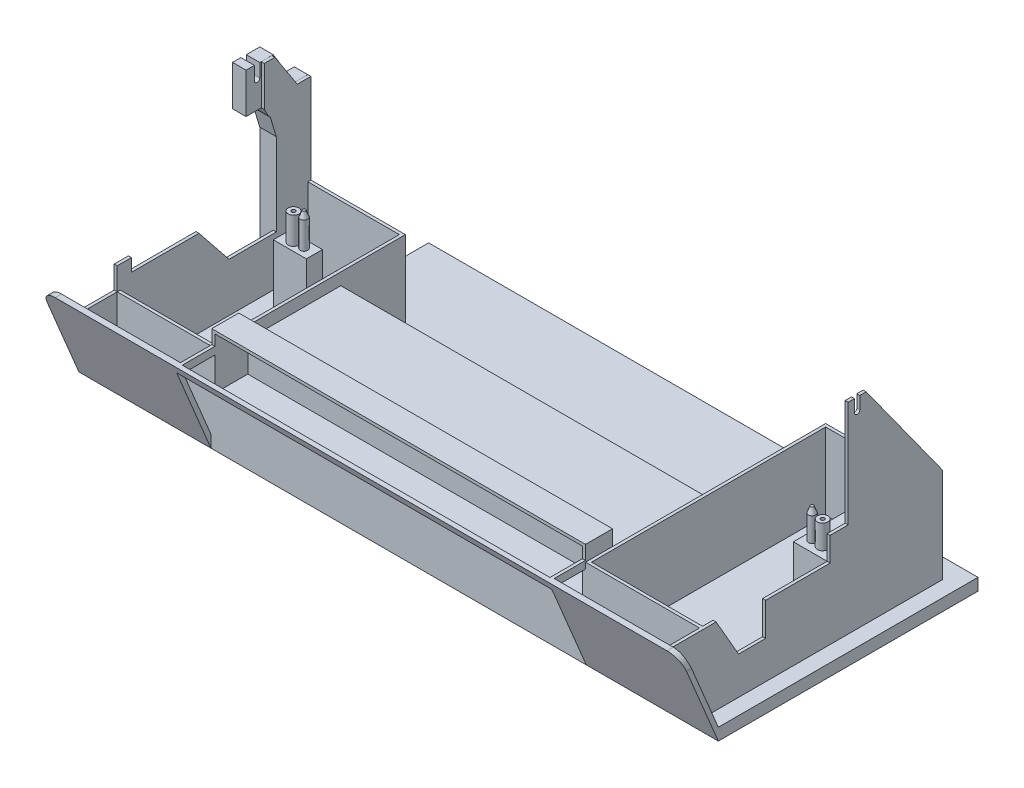
SolidWorks part; units mm, degrees
ref_plane "Alzado" through (0, 0, 0) normal (0, 0, 1) x (1, 0, 0)
ref_plane "Planta" through (0, 0, 0) normal (0, 1, 0) x (1, 0, 0)
ref_plane "Vista lateral" through (0, 0, 0) normal (1, 0, 0) x (0, 0, -1)
sketch "Croquis1" plane through (0, 0, 0) normal (0, 1, 0) x (1, 0, 0)
  line L1 (213, -91.5) -> (-213, -91.5)
  line L2 (213, -91.5) -> (213, 91.5)
  line L3 (213, 91.5) -> (-213, 91.5)
  line L4 (-213, -91.5) -> (-213, 91.5)
  line L5 (213, -91.5) -> (-213, 91.5) construction
  line L6 (213, 91.5) -> (-213, -91.5) construction
  line L7 (213, 91.5) -> (163, 91.5)
  line L8 (213, 91.5) -> (213, 81.5)
  line L9 (213, 81.5) -> (163, 81.5)
  line L10 (163, 91.5) -> (163, 81.5)
  line L11 (-213, 91.5) -> (-163, 91.5)
  line L12 (-213, 91.5) -> (-213, 46.5)
  line L13 (-213, 46.5) -> (-163, 46.5)
  line L14 (-163, 91.5) -> (-163, 46.5)
  point P0 (0, 0)
  dimension "D1" = 183
  dimension "D2" = 426
  dimension "D3" = 10
  dimension "D4" = 50
  dimension "D5" = 45
  dimension "D6" = 50
extrude "Saliente-Extruir3" add sketch "Croquis1" along normal blind 8 contours L3 L14 L13 L4 L1 L2 L9 L10 region at (4.3745, 0, 2.6393)
sketch "Croquis4" plane through (0, 0, 0) normal (0, -1, 0) x (1, 0, 0)
  line L1 (-213, 91.5) -> (212.5, 91.5)
  line L2 (-213, 91.5) -> (-213, 117.5)
  line L3 (-213, 117.5) -> (212.5, 117.5)
  line L4 (212.5, 91.5) -> (212.5, 117.5)
  dimension "D1" = 26
extrude "Saliente-Extruir5" add sketch "Croquis4" against normal blind 70 separate body
sketch "Croquis5" plane through (-213, 0, 0) normal (-1, 0, 0) x (0, 0, 1)
  line L0 (91.5, 8) -> (91.5, 5.5)
  line L2 (91.5, 8) -> (98.5, 8)
  line L3 (91.5, 70) -> (91.5, 0) construction
  line L4 (91.5, 5.5) -> (99.5, 5.5)
  line L10 (117.5, 0) -> (91.5, 0) construction
  line L11 (91.5, 70) -> (117.5, 70)
  line L12 (91.5, 70) -> (91.5, 0)
  line L13 (91.5, 0) -> (117.5, 0)
  line L14 (117.5, 70) -> (117.5, 0)
  line L15 (117.5, 70) -> (115, 70)
  line L16 (115, 70) -> (98.5, 8)
  line L17 (99.5, 5.5) -> (117.5, 70)
  line M12 (91.5, 0) -> (117.5, 0)
  line M13 (117.5, 0) -> (117.5, 70)
  line M15 (91.5, 70) -> (91.5, 0)
  dimension "D1" = 2.5
  dimension "D2" = 8
  dimension "D3" = 2.5
extrude "Cortar-Extruir5" cut sketch "Croquis5" against normal through all contours L16 L11 L2 M15 | L17 L4 M15 M12 M13 region at (-213, 44.5902, 99.8689) region at (-213, 22.207, 110.1164)
fillet "Redondeo2" radius 1 3 edges at (-0.25, 70, 115) (-0.25, 70, 117.5) (-0.25, 5.5, 99.5)
sketch "Croquis7" plane through (0, 0, 91.5) normal (0, 0, 1) x (1, 0, 0)
  line L1 (213, 0) -> (-213, 0) construction
  line L3 (-122.5, 0) -> (122.5, 0)
  line L4 (-122.5, 0) -> (-122.5, 65)
  line L5 (-122.5, 65) -> (122.5, 65)
  line L6 (122.5, 0) -> (122.5, 65)
  dimension "D2" = 65
  dimension "D3" = 245
extrude "Cortar-Extruir6" cut sketch "Croquis7" along normal blind 25
sketch "Croquis8" plane through (0, 8, 0) normal (0, 1, 0) x (1, 0, 0)
  line L1 (-122.5, -91.5) -> (122.5, -91.5)
  line L2 (-122.5, -91.5) -> (-122.5, -69.5)
  line L3 (-122.5, -69.5) -> (122.5, -69.5)
  line L4 (122.5, -91.5) -> (122.5, -69.5)
  dimension "D1" = 22
extrude "Saliente-Extruir6" add sketch "Croquis8" along normal blind 25
sketch "Croquis9" plane through (-122.5, 0, 0) normal (-1, 0, 0) x (0, 0, 1)
  line L2 (114.8023, 69.2572) -> (98.5, 8)
  line L4 (98.5, 8) -> (73.5, 8)
  line L5 (98.5, 8) -> (-46.5, 8) construction
  line L6 (73.5, 8) -> (73.5, 69.2572)
  line L7 (73.5, 69.2572) -> (114.8023, 69.2572)
  dimension "D1" = 25
extrude "Saliente-Extruir7" add sketch "Croquis9" along normal blind 2
sketch "Croquis10" plane through (122.5, 0, 0) normal (1, 0, 0) x (0, 0, -1)
  line L5 (-91.5, 8) -> (-69.5, 8) construction
  line L6 (-73.5, 8) -> (-73.5, 69.2572)
  line L8 (-73.5, 69.2572) -> (-114.8023, 69.2572)
  line L9 (-114.8023, 69.2572) -> (-98.5, 8)
  line L10 (-98.5, 8) -> (-73.5, 8)
extrude "Saliente-Extruir8" add sketch "Croquis10" along normal blind 2
sketch "Croquis13" plane through (-122.5, 0, 0) normal (1, 0, 0) x (0, 0, -1)
  line L2 (-114.8023, 69.2572) -> (-114.8023, 67.2572)
  line L5 (-114.8023, 69.2572) -> (-73.5, 69.2572)
  line L6 (-73.5, 69.2572) -> (-73.5, 67.2572)
  line L7 (-73.5, 69.2572) -> (-73.5, 33) construction
  line L8 (-114.8023, 67.2572) -> (-73.5, 67.2572)
  dimension "D1" = 2
extrude "Saliente-Extruir13" add sketch "Croquis13" along normal up to surface (245 mm away) up to face at (122.5, 39.0648, 97.016)
sketch "Croquis15" plane through (0, 8, 0) normal (0, 1, 0) x (1, 0, 0)
  line L1 (213, -91.5) -> (213, 81.5) construction
  line L2 (213, -73.5) -> (213, -71.5)
  line L15 (124.5, -91.5) -> (202.5, -91.5)
  line L21 (124.5, -98.5) -> (124.5, -91.5)
  line L22 (124.5, -98.5) -> (124.5, -73.5) construction
  line L26 (202.5, -91.5) -> (202.5, 68.5)
  line L28 (126.5, -89.5) -> (200.5, -89.5)
  line L30 (202.5, 68.5) -> (124.5, 68.5)
  line L31 (124.5, -91.5) -> (124.5, 68.5)
  line L32 (124.5, 68.5) -> (124.5, 66.5) construction
  line L33 (124.5, 66.5) -> (126.5, 66.5) construction
  line L34 (126.5, 66.5) -> (126.5, -89.5)
  line L35 (126.5, 66.5) -> (200.5, 66.5)
  line L36 (200.5, 66.5) -> (200.5, -89.5)
  dimension "D2" = 160
  dimension "D1" = 7
  dimension "D3" = 2
  dimension "D4" = 2
extrude "Saliente-Extruir15" add sketch "Croquis15" along normal blind 51 contours L15 L26 L30 L31 | L28 L36 L35 L34
sketch "Croquis16" plane through (0, 8, 0) normal (0, 1, 0) x (1, 0, 0)
  line L1 (-122.5, -69.5) -> (122.5, -69.5)
  line L2 (-122.5, -69.5) -> (-122.5, -5.5)
  line L3 (-122.5, -5.5) -> (122.5, -5.5)
  line L4 (122.5, -69.5) -> (122.5, -5.5)
  dimension "D1" = 64
extrude "Saliente-Extruir16" add sketch "Croquis16" along normal blind 43
sketch "Croquis17" plane through (0, 8, 0) normal (0, 1, 0) x (1, 0, 0)
  line L1 (122.5, -5.5) -> (124.5, -5.5)
  line L2 (122.5, -5.5) -> (122.5, -73.5)
  line L3 (122.5, -73.5) -> (124.5, -73.5)
  line L4 (124.5, -5.5) -> (124.5, -73.5)
  line L6 (124.5, -73.5) -> (124.5, 68.5) construction
  line L7 (124.5, -73.5) -> (122.5, -73.5) construction
  dimension "D1" = 68
extrude "Saliente-Extruir18" add sketch "Croquis17" along normal up to surface (43 mm away) up to face at (0, 51, 37.5)
sketch "Croquis18" plane through (202.5, 0, 0) normal (1, 0, 0) x (0, 0, -1)
  line L0 (-91.5, 8) -> (-98.5, 8)
  line L1 (-98.5, 8) -> (-112.0726, 59)
  line L2 (-114.8023, 69.2572) -> (-98.5, 8) construction
  line L3 (-112.0726, 59) -> (-91.5, 59)
  line L4 (-91.5, 59) -> (-91.5, 8)
extrude "Saliente-Extruir21" add sketch "Croquis18" against normal blind 2
sketch "Croquis20" plane through (0, 59, 0) normal (0, 1, 0) x (1, 0, 0)
  line L1 (200.5, -91.5) -> (202.5, -91.5)
  line L2 (200.5, -91.5) -> (200.5, 68.5)
  line L3 (200.5, 68.5) -> (202.5, 68.5)
  line L4 (202.5, -91.5) -> (202.5, 68.5)
extrude "Saliente-Extruir22" add sketch "Croquis20" along normal blind 100
sketch "Croquis21" plane through (202.5, 0, 0) normal (1, 0, 0) x (0, 0, -1)
  line L0 (-91.5, 59) -> (-82.5, 59)
  line L3 (-67.5, 33) -> (-82.5, 59)
  line L4 (-67.5, 33) -> (-49.5, 33)
  line L5 (-49.5, 33) -> (-49.5, 55)
  line L6 (-49.5, 55) -> (-6.5, 55)
  line L7 (-6.5, 55) -> (-6.5, 71)
  line L8 (-6.5, 71) -> (5.5, 71)
  line L9 (5.5, 71) -> (5.5, 141.8)
  line L11 (17.5, 141.8) -> (68.5, 71)
  line L12 (68.5, 159) -> (68.5, 8) construction
  line L13 (-91.5, 59) -> (-91.5, 159)
  line L14 (-91.5, 159) -> (68.5, 159)
  line L15 (68.5, 159) -> (68.5, 71)
  line L16 (5.5, 141.8) -> (9.7, 141.8)
  line L17 (9.7, 141.8) -> (9.7, 133.6)
  line L18 (17.5, 141.8) -> (13.3, 141.8)
  line L19 (13.3, 141.8) -> (13.3, 133.6)
  line L20 (-82.5, 59) -> (-82.5, 33) construction
  line L21 (-82.5, 33) -> (-67.5, 33) construction
  arc A0 (9.7, 133.6) -> (13.3, 133.6) centre (11.5, 133.6) ccw
  dimension "D12" = 6
  dimension "D1" = 9
  dimension "D2" = 18
  dimension "D3" = 22
  dimension "D4" = 43
  dimension "D5" = 16
  dimension "D6" = 12
  dimension "D7" = 70.8
  dimension "D8" = 12
  dimension "D9" = 4.2
  dimension "D10" = 8.2
  dimension "D11" = 4.2
  dimension "D13" = 26
extrude "Cortar-Extruir7" cut sketch "Croquis21" against normal blind 2
sketch "Croquis22" plane through (0, 8, 0) normal (0, 1, 0) x (1, 0, 0)
  line L1 (-124.5, -73.5) -> (-122.5, -73.5)
  line L2 (-124.5, -73.5) -> (-124.5, -5.5)
  line L3 (-124.5, -5.5) -> (-122.5, -5.5)
  line L4 (-122.5, -73.5) -> (-122.5, -5.5)
extrude "Saliente-Extruir23" add sketch "Croquis22" along normal up to surface (43 mm away) up to face at (41.5, 51, 49.5)
sketch "Croquis23" plane through (0, 8, 0) normal (0, 1, 0) x (1, 0, 0)
  line L0 (-124.5, -91.5) -> (-124.5, -89.5) construction
  line L1 (-124.5, -98.5) -> (-124.5, -91.5) construction
  line L2 (-124.5, -5.5) -> (-124.5, -98.5) construction
  line L3 (-124.5, -89.5) -> (-126.5, -89.5) construction
  line L4 (-124.5, -91.5) -> (-189.5, -91.5)
  line L5 (-124.5, -91.5) -> (-124.5, 37.5)
  line L6 (-124.5, 37.5) -> (-189.5, 37.5)
  line L7 (-189.5, -91.5) -> (-189.5, 37.5)
  line L9 (-126.5, -89.5) -> (-187.5, -89.5)
  line L10 (-126.5, -89.5) -> (-126.5, 35.5)
  line L11 (-126.5, 35.5) -> (-187.5, 35.5)
  line L12 (-187.5, -89.5) -> (-187.5, 35.5)
  dimension "D1" = 7
  dimension "D2" = 129
  dimension "D3" = 65
  dimension "D4" = 2
  dimension "D5" = 2
  dimension "D6" = 125
  dimension "D7" = 61
extrude "Saliente-Extruir24" add sketch "Croquis23" along normal up to surface (51 mm away) up to face at (171.8846, 59, 42.665)
sketch "Croquis26" plane through (-189.5, 0, 0) normal (-1, 0, 0) x (0, 0, 1)
  line L0 (91.5, 8) -> (98.5, 8)
  line L5 (91.5, 59) -> (91.5, 8)
  line L6 (91.5, 59) -> (112.0726, 59)
  line L7 (114.8023, 69.2572) -> (98.5, 8) construction
  line L8 (112.0726, 59) -> (98.5, 8)
extrude "Saliente-Extruir26" add sketch "Croquis26" against normal blind 2
sketch "Croquis27" plane through (0, 51, 0) normal (0, 1, 0) x (1, 0, 0)
  line L7 (-189.5, 37.5) -> (-187.5, 37.5)
  line L8 (-189.5, 37.5) -> (-189.5, -91.5)
  line L9 (-189.5, -91.5) -> (-187.5, -91.5)
  line L10 (-187.5, 37.5) -> (-187.5, -91.5)
extrude "Saliente-Extruir27" add sketch "Croquis27" along normal blind 150
sketch "Croquis28" plane through (-189.5, 0, 0) normal (-1, 0, 0) x (0, 0, 1)
  line L0 (91.5, 59) -> (91.5, 74)
  line L1 (91.5, 201) -> (91.5, 59) construction
  line L2 (91.5, 74) -> (82, 74)
  line L3 (82, 74) -> (82, 65.5)
  line L4 (82, 65.5) -> (37, 65.5)
  line L7 (17, 40.5) -> (37, 65.5)
  line L8 (-37.5, 40.5) -> (-14.5, 40.5) construction
  line L9 (-37.5, 201) -> (-37.5, 8) construction
  line L10 (17, 40.5) -> (-14.5, 40.5)
  line L11 (-14.5, 40.5) -> (-14.5, 95.5)
  line L13 (-37.5, 118.7922) -> (-37.5, 201)
  line L17 (-28.5, 118.7922) -> (-13.5, 141.7922)
  line L18 (-28.5, 118.7922) -> (-37.5, 118.7922)
  line L19 (-14.5, 95.5) -> (-10.5263, 108.6789)
  line L22 (-37.5, 201) -> (91.5, 201)
  line L23 (91.5, 201) -> (91.5, 74)
  line L29 (-37.5, 118.7922) -> (-37.5, 201)
  line L30 (91.5, 201) -> (91.5, 74)
  line L31 (-13.5, 141.7922) -> (-13.5, 118.7922) construction
  line L32 (-10.5263, 108.6789) -> (-8.9353, 110.5946)
  line L33 (-13.5, 141.7922) -> (-6.5, 141.7922)
  line L34 (-13.5, 118.7922) -> (-28.5, 118.7922) construction
  line L35 (-6.5, 141.7922) -> (-6.5, 115.1522)
  line L36 (-6.5, 115.1522) -> (-8.9353, 110.5946)
  line L37 (-37.5, 118.7922) -> (-37.5, 8)
  line L38 (-37.5, 8) -> (-37.5, 118.7922)
  line M3 (91.5, 59) -> (91.5, 201)
  line M4 (91.5, 201) -> (-37.5, 201)
  line M5 (-37.5, 201) -> (-37.5, 8)
  dimension "D5" = 23
  dimension "D1" = 15
  dimension "D2" = 9.5
  dimension "D3" = 8.5
  dimension "D4" = 45
  dimension "D6" = 55
  dimension "D7" = 7
extrude "Cortar-Extruir9" cut sketch "Croquis28" against normal blind 2 contours L19 L11 L10 L7 L4 L3 L2 L18 L17 M3 M4 M5 region at (-189.5, 131.8802, 30.3674)
sketch "Croquis29" plane through (-189.5, 0, 0) normal (-1, 0, 0) x (0, 0, 1)
  line L1 (-37.5, 8) -> (-14.5, 8)
  line L2 (-37.5, 8) -> (-37.5, 118.8)
  line L11 (-14.5, 95.5) -> (-14.5, 8)
  line L33 (-14.5, 95.5) -> (-10.5263, 108.6789)
  line L41 (-10.5263, 108.6789) -> (-8.9353, 110.5946)
  line L42 (-8.9353, 110.5946) -> (-6.5, 115.1522)
  line L43 (-6.5, 115.1522) -> (3.6557, 115.1522)
  line L45 (-37.5, 118.8) -> (-28.5, 118.8)
  line L48 (-5.5, 71) -> (-5.5, 141.8) construction
  line L51 (-1.9, 132.9522) -> (-1.9, 141.9522)
  line L52 (-1.9, 141.9522) -> (3.6557, 141.9522)
  line L53 (3.6557, 141.9522) -> (3.6557, 115.1522)
  line L54 (-5.5, 132.9522) -> (-5.5, 141.8)
  line L55 (-5.5, 141.8) -> (-14.5, 141.8)
  line L56 (-14.5, 141.8) -> (-28.5, 118.8)
  arc A2 (-5.5, 132.9522) -> (-1.9, 132.9522) centre (-3.7, 132.9522) ccw
  dimension "D5" = 26.8
  dimension "D1" = 110.8
  dimension "D2" = 23
  dimension "D3" = 9
  dimension "D4" = 3.6
extrude "Saliente-Extruir28" add sketch "Croquis29" along normal blind 9
sketch "Croquis33" plane through (0, 8, 0) normal (0, 1, 0) x (1, 0, 0)
  line L0 (-124.5, 37.5) -> (-124.5, 1.87) construction
  line L1 (-124.5, -5.5) -> (-124.5, 37.5) construction
  line L2 (-124.5, 1.87) -> (-149.5, 1.87) construction
  line L3 (-149.5, -3.48) -> (-149.5, 7.22)
  line L4 (-149.5, 7.22) -> (-171.5, 7.22)
  line L5 (-171.5, 7.22) -> (-171.5, -3.48)
  line L6 (-171.5, -3.48) -> (-149.5, -3.48)
  point P9 (-149.5, 1.87)
  dimension "D1" = 35.63
  dimension "D2" = 25
  dimension "D3" = 5.35
  dimension "D4" = 22
extrude "Saliente-Extruir29" add sketch "Croquis33" along normal blind 45
sketch "Croquis34" plane through (0, 53, 0) normal (0, 1, 0) x (1, 0, 0)
  line L0 (-159.9, 3) -> (-158.9, 3)
  line L1 (-171.5, -3.48) -> (-171.5, 1.87) construction
  line L2 (-158.9, 3) -> (-156.4, 3)
  line L3 (-171.5, 7.22) -> (-171.5, -3.48) construction
  line L4 (-171.5, 1.87) -> (-163.4, 1.87) construction
  line L6 (-156.4, 1.87) -> (-163.4, 1.87) construction
  circle A3 centre (-163.4, 1.87) radius 1.25
  circle A4 centre (-163.4, 1.87) radius 3.5
  circle A5 centre (-156.4, 1.87) radius 2.5
  dimension "D3" = 7
  dimension "D1" = 2.5
  dimension "D5" = 5
  dimension "D2" = 1
  dimension "D4" = 2.5
extrude "Saliente-Extruir30" add sketch "Croquis34" along normal blind 18 contours A3 | A5 region at (-166.801, 53, -1.87)
sketch "Croquis36" plane through (200.5, 0, 0) normal (-1, 0, 0) x (0, 0, 1)
  line L7 (6.5, 55) -> (-29, 55)
  line L12 (6.5, 55) -> (6.5, 8)
  line L13 (6.5, 8) -> (-29, 8)
  line L14 (-29, 55) -> (-29, 8)
  line L15 (-66.5, 8) -> (89.5, 8) construction
  dimension "D1" = 47
  dimension "D2" = 35.5
extrude "Saliente-Extruir34" add sketch "Croquis36" along normal blind 22.5
sketch "Croquis37" plane through (0, 71, 0) normal (0, 1, 0) x (1, 0, 0)
  line L0 (202.5, 5.5) -> (202.5, 0.5) construction
  line L1 (202.5, -6.5) -> (202.5, 5.5) construction
  line L2 (202.5, 0.5) -> (194, 0.5) construction
  line L3 (194, 0.5) -> (190.5, 0.5) construction
  line L4 (187, 0.5) -> (186, 0.5)
  line L5 (186, 0.5) -> (183.5, 0.5)
  circle A0 centre (190.5, 0.5) radius 3.5
  circle A1 centre (183.5, 0.5) radius 2.5
  circle A2 centre (190.5, 0.5) radius 1.25
  dimension "D4" = 7
  dimension "D7" = 5
  dimension "D8" = 2.5
  dimension "D1" = 5
  dimension "D2" = 8.5
  dimension "D3" = 3.5
  dimension "D5" = 1
  dimension "D6" = 2.5
extrude "Saliente-Extruir35" add sketch "Croquis37" against normal up to next contours A0 A2 | A1 region at (181.0707, 71, -0.5) region at (190.5, 71, -3.901)
sketch "Croquis39" plane through (0, 71, 0) normal (0, 1, 0) x (1, 0, 0)
  circle A0 centre (-156.4, 1.87) radius 1
  dimension "D1" = 2
extrude "Saliente-Extruir37" add sketch "Croquis39" along normal blind 4
loft "Recubrir3" add section edge at (-156.4, 71, 0.63) section edge at (-156.4, 75, -0.87) connector at (-157.8182, 71, 0.1888) connector at (-156.4778, 75, -0.873)
sketch "Croquis41" plane through (0, 71, 0) normal (0, 1, 0) x (1, 0, 0)
  circle A0 centre (183.5, 0.5) radius 1
  dimension "D1" = 2
extrude "Saliente-Extruir38" add sketch "Croquis41" along normal blind 4
loft "Recubrir4" add section edge at (183.5, 75, 0.5) section edge at (183.5, 71, 2) connector at (184.219, 75, 0.195) connector at (184.2201, 71, 1.8941)
sketch "Croquis42" plane through (-213, 0, 0) normal (-1, 0, 0) x (0, 0, 1)
  line L0 (91.5, 0) -> (91.5, 60)
  line L1 (91.5, 60) -> (116.5, 60)
  line L2 (116.5, 60) -> (91.5, 0)
  line L3 (91.5, 0) -> (91.5, 8)
  line L4 (98.5, 8) -> (-46.5, 8) construction
  line L5 (91.5, 8) -> (113.1667, 60)
  line M5 (91.5, 0) -> (91.5, 5.5)
  line M6 (91.5, 5.5) -> (98.7409, 5.5)
  line M8 (99.7041, 6.2312) -> (117.1459, 68.7312)
  line M12 (114.8023, 69.2572) -> (98.5, 8)
  line M13 (98.5, 8) -> (-46.5, 8)
  dimension "D1" = 60
  dimension "D2" = 25
extrude "Saliente-Extruir39" add sketch "Croquis42" against normal through all contours L2 L1 M8 | L5 L2 L1 M12 M8 | L5 L2 M13 M12 | L2 L0 M13 M6 | L2 M6 M5 region at (-213, 3.6667, 92.2639) region at (-213, 6.8272, 92.9223) region at (-213, 26.2909, 100.6143) region at (-213, 49.0965, 110.4746) region at (-213, 55.662, 114.0956)
sketch "Croquis43" plane through (-213, 0, 0) normal (-1, 0, 0) x (0, 0, 1)
  line L0 (116.5, 60) -> (91.5, 0)
  line L1 (116.5, 60) -> (116.5, 0)
  line L2 (116.5, 0) -> (91.5, 0)
extrude "Cortar-Extruir10" cut sketch "Croquis43" against normal through all
sketch "Croquis44" plane through (-213, 0, 0) normal (-1, 0, 0) x (0, 0, 1)
  line L0 (91.5, 74) -> (91.5, 59) construction
  line L1 (116.5, 60) -> (91.5, 60)
  line L3 (116.5, 70.5118) -> (91.5, 70.5118)
  line L4 (91.5, 60) -> (91.5, 70.5118)
  line L6 (116.5, 70.5118) -> (118.3191, 70.5118)
  line L8 (116.5, 60) -> (118.3191, 60)
  line L9 (118.3191, 70.5118) -> (118.3191, 60)
extrude "Cortar-Extruir11" cut sketch "Croquis44" against normal through all
sketch "Croquis46" plane through (0, 0, 91.5) normal (0, 0, 1) x (1, 0, 0)
  line L0 (125, 0) -> (-125, 0)
  line L1 (213, 0) -> (-213, 0) construction
  line L2 (-125, 0) -> (-125, 55)
  line L3 (-125, 55) -> (125, 55)
  line L4 (125, 55) -> (125, 0)
  point P5 (0, 0)
  dimension "D1" = 55
extrude "Cortar-Extruir12" cut sketch "Croquis46" along normal through all
sketch "Croquis47" plane through (0, 0, 91.5) normal (0, 0, 1) x (1, 0, 0)
  line L0 (0, 0) -> (-213, 0) construction
  line L1 (-125, 0) -> (125, 0) construction
  line L2 (-213, 0) -> (-213, 50.8) construction
  line L3 (213, 60) -> (-213, 60) construction
  line L4 (-213, 50.8) -> (-213, 60)
  line L5 (-213, 60) -> (-203.8, 60)
  line L6 (0, 0) -> (213, 0) construction
  line L7 (213, 0) -> (213, 50.8) construction
  line L8 (213, 60) -> (213, 0) construction
  line L9 (203.8, 60) -> (213, 60)
  line L10 (213, 60) -> (213, 50.8)
  arc A0 (-213, 50.8) -> (-203.8, 60) centre (-203.8, 50.8) cw
  arc A1 (213, 50.8) -> (203.8, 60) centre (203.8, 50.8) ccw
  dimension "D2" = 50.8
  dimension "D1" = 50.8
extrude "Cortar-Extruir16" cut sketch "Croquis47" along normal through all contours L10 A1 L9 | L5 A0 L4
